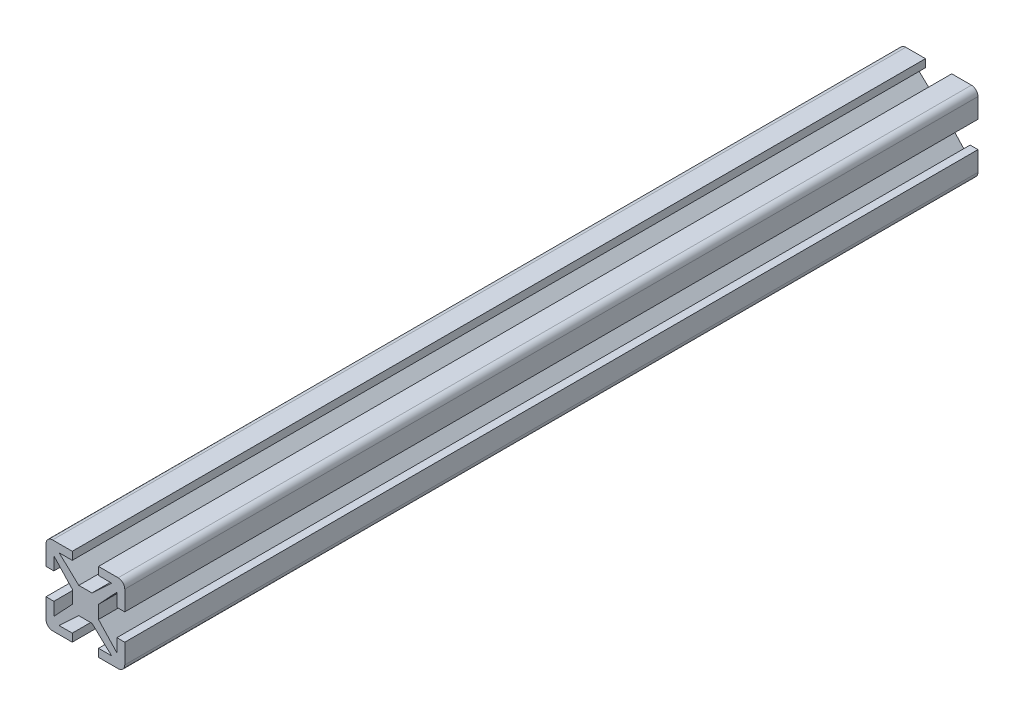
SolidWorks part; units mm, degrees
ref_plane "Plan de face" through (0, 0, 0) normal (0, 0, 1) x (1, 0, 0)
ref_plane "Plan de dessus" through (0, 0, 0) normal (0, 1, 0) x (1, 0, 0)
ref_plane "Plan de droite" through (0, 0, 0) normal (1, 0, 0) x (0, 0, -1)
sketch "Esquisse1" plane through (0, 0, 0) normal (0, 0, 1) x (1, 0, 0)
  line L0 (-6, 5) -> (-6, -5)
  line L1 (-5, 6) -> (5, 6)
  line L2 (-5, -6) -> (5, -6)
  line L3 (6, 5) -> (6, -5)
  line L4 (-5, 5) -> (5, -5) construction
  line L5 (5, 5) -> (-5, -5) construction
  arc A0 (-5, 6) -> (-6, 5) centre (-5, 5) ccw
  arc A1 (5, 6) -> (6, 5) centre (5, 5) cw
  arc A2 (6, -5) -> (5, -6) centre (5, -5) cw
  arc A3 (-5, -6) -> (-6, -5) centre (-5, -5) cw
  point P12 (0, 0)
  dimension "D1" = 1
  dimension "D2" = 1
  dimension "D4" = 1
  dimension "D3" = 12
extrude "Extrusion1" add sketch "Esquisse1" along normal mid plane 130
sketch "Esquisse3" plane through (0, 0, 65) normal (0, 0, 1) x (1, 0, 0)
  line L0 (6, 2) -> (4.8, 2)
  line L2 (4.8, 2) -> (4.8, 4)
  line L3 (2, 1) -> (2, -1)
  line L4 (4.8, -4) -> (4.8, -2)
  line L5 (4.8, -2) -> (6, -2)
  line L6 (6, -5) -> (6, 5) construction
  line L7 (4.8, 4) -> (2, 1)
  line L8 (6, 2) -> (6, -2)
  line L9 (4.8, -4) -> (2, -1)
  point P4 (6, 0)
  point P10 (6, 0)
  dimension "D1" = 4
  dimension "D2" = 1.2
  dimension "D3" = 4
  dimension "D4" = 2
  dimension "D5" = 2
extrude "Enlèv. mat.-Extru.1" cut sketch "Esquisse3" against normal through all
ref_axis "Axe1" through (0, 0, -1) along (0, 0, 1)
pattern_circular "Répétition circulaire1" count 4 every 90 about axis through (0, 0, -1) along (0, 0, 1) of "Enlèv. mat.-Extru.1"
